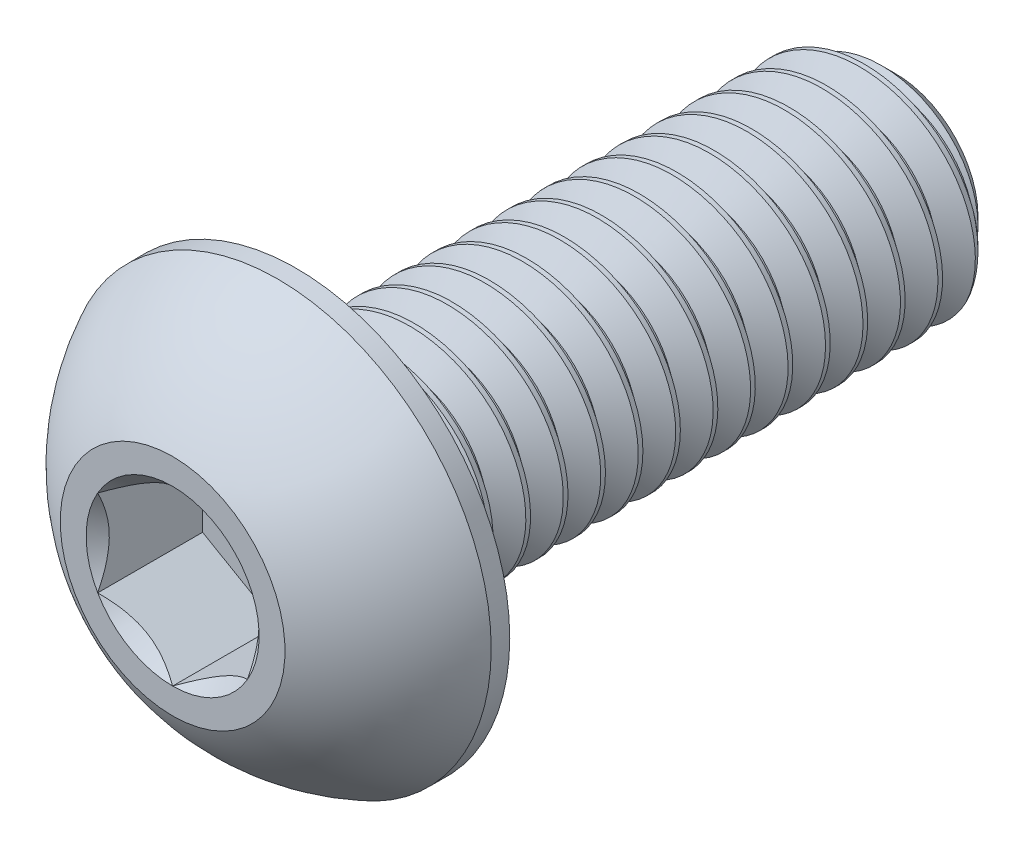
SolidWorks part; units mm, degrees
material "Stainless Steel (ferritic)"
ref_plane "Front Plane" through (0, 0, 0) normal (0, 0, 1) x (1, 0, 0)
ref_plane "Top Plane" through (0, 0, 0) normal (0, 1, 0) x (1, 0, 0)
ref_plane "Right Plane" through (0, 0, 0) normal (1, 0, 0) x (0, 0, -1)
sketch "Sketch1" plane through (0, 0, 0) normal (1, 0, 0) x (0, 0, -1)
  line L0 (-4.825, 0) -> (4.825, 0) construction
  line L1 (-3.175, 2.85) -> (-3.175, -2.85) construction
  line L2 (4.825, 1.5) -> (4.825, -1.5) construction
  line L3 (4.7937, 1.5541) -> (5.0437, 1.1211) construction
  line L4 (5.0437, 1.1211) -> (5.2938, 1.5541) construction
  line L5 (5.2938, 1.5541) -> (4.7937, 1.5541) construction
  line L6 (4.825, 1.5) -> (5.2625, 1.5) construction
  line L7 (5.0437, 1.5541) -> (5.0437, 1.5) construction
  line L8 (5.0437, 1.5) -> (5.0437, 1.1752) construction
  line L9 (5.0437, 1.1752) -> (5.0437, 1.1211) construction
  line L10 (5.0125, 1.1752) -> (5.075, 1.1752)
  line L11 (4.8094, 1.5271) -> (5.2781, 1.5271)
  line L12 (5.075, 1.1752) -> (5.2781, 1.5271)
  line L13 (5.0125, 1.1752) -> (4.8094, 1.5271)
  line L14 (-4.825, 1) -> (-4.825, -1) construction
  line L15 (4.825, 1.5) -> (-3.175, 1.5) construction
  point P3 (-3.175, 0)
  point P6 (-3.425, 0)
  point P21 (5.0437, 1.5271)
  point P24 (-3.4225, 2.85)
  point P25 (3.575, -1.5)
  point P26 (-4.825, 1.5)
  dimension "Head Height" = 1.65
  dimension "Length" = 8
  dimension "Head Dia" = 5.7
  dimension "Thread Dia" = 3
  dimension "Pitch" = 0.5
  dimension "Drive Size" = 2
  dimension "D1" = 1.4
  dimension "D3" = 0.2475
  dimension "D4" = 1.25
sketch "Sketch2" plane through (0, 0, 0) normal (1, 0, 0) x (0, 0, -1)
  line L0 (-4.825, 0) -> (4.825, 0)
  line L1 (4.825, 0) -> (4.825, 1.1)
  line L2 (4.825, 1.5) -> (4.825, -1.5) construction
  line L3 (4.825, 1.1) -> (4.425, 1.5)
  line L4 (4.425, 1.5) -> (-3.175, 1.5)
  line L5 (-3.175, 2.85) -> (-3.175, -2.85) construction
  line L6 (-3.175, 1.5) -> (-3.175, 2.85)
  line L7 (-3.175, 2.85) -> (-3.4225, 2.85)
  line L8 (4.825, 1.5) -> (5.2625, 1.5) construction
  line L9 (-4.825, 0) -> (-4.825, 1.5)
  arc A0 (-4.825, 1.5) -> (-3.4225, 2.85) centre (-2.0302, 0) cw
  dimension "D1" = 0.4
  dimension "D2" = 45
revolve "Revolve1" add sketch "Sketch2" angle 360 about L0
sketch "Sketch3" plane through (0, 0, 4.825) normal (0, 0, 1) x (1, 0, 0)
  line L1 (0, 1.1547) -> (-1, 0.5774)
  line L2 (-1, 0.5774) -> (-1, -0.5774)
  line L3 (-1, -0.5774) -> (0, -1.1547)
  line L4 (0, -1.1547) -> (1, -0.5774)
  line L5 (1, -0.5774) -> (1, 0.5774)
  line L6 (1, 0.5774) -> (0, 1.1547)
  circle A0 centre (0, 0) radius 1 construction
  dimension "D1" = 2
extrude "Cut-Extrude1" cut sketch "Sketch3" against normal up to vertex (1.4 mm away) up to point (0, 0, 3.425)
sketch "Sketch4" plane through (0, 0, 4.825) normal (0, 0, 1) x (1, 0, 0)
  circle A0 centre (0, 0) radius 1.1547
extrude "Cut-Extrude2" cut sketch "Sketch4" against normal blind 10 draft 45
split "Split1" bodies to split 106 resulting bodies 107 108 split by face at (2.85, 0, 3.175)
sketch "Sketch5" plane through (0, 0, -4.825) normal (0, 0, -1) x (-1, 0, 0)
  circle A0 centre (0, 0) radius 1.5 construction
  circle A1 centre (0, 0) radius 1.5
curve "Helix/Spiral1" pitch 0.5 height 8.5 radius 1.5 centre (0, 0, -4.825) axis (0, 0, 1) start towards (0, 1, 0)
sketch "Sketch6" plane through (0, 0, 0) normal (1, 0, 0) x (0, 0, -1)
  line L0 (5.0125, 1.1752) -> (5.075, 1.1752) construction
  line L1 (5.0125, 1.1752) -> (4.8094, 1.5271) construction
  line L2 (4.8094, 1.5271) -> (5.2781, 1.5271) construction
  line L3 (5.075, 1.1752) -> (5.2781, 1.5271) construction
  line L4 (5.0125, 1.1752) -> (5.075, 1.1752)
  line L5 (5.0125, 1.1752) -> (4.8094, 1.5271)
  line L6 (4.8094, 1.5271) -> (5.2781, 1.5271)
  line L7 (5.075, 1.1752) -> (5.2781, 1.5271)
sweep "Cut-Sweep1" cut profiles "Sketch6" path "Helix/Spiral1" align with end faces yes
sketch "Sketch7" plane through (0, 0, 3.175) normal (0, 0, -1) x (-1, 0, 0)
  circle A1 centre (0, 0) radius 1.5
  circle A2 centre (0, 0) radius 1.5
  dimension "D1" = 0
extrude "Boss-Extrude1" add sketch "Sketch7" along normal blind 10 draft 30
equation "\"D2@Sketch1\" = \"Pitch@Sketch1\" / 8"
equation "\"D1@Sketch1\"=\"Drive Size@Sketch1\"*.7"
equation "\"D3@Sketch1\"=\"Head Height@Sketch1\"*.15"
equation "\"D1@Sketch2\"=\"Pitch@Sketch1\"*.8"
equation "\"D1@Sketch3\"=\"Drive Size@Sketch1\""
equation "\"D4@Helix/Spiral1\"=\"Pitch@Sketch1\""
equation "\"D3@Helix/Spiral1\"=\"Length@Sketch1\"+\"Pitch@Sketch1\""
equation "\"D4@Sketch1\"=\"Pitch@Sketch1\"*2.5"
